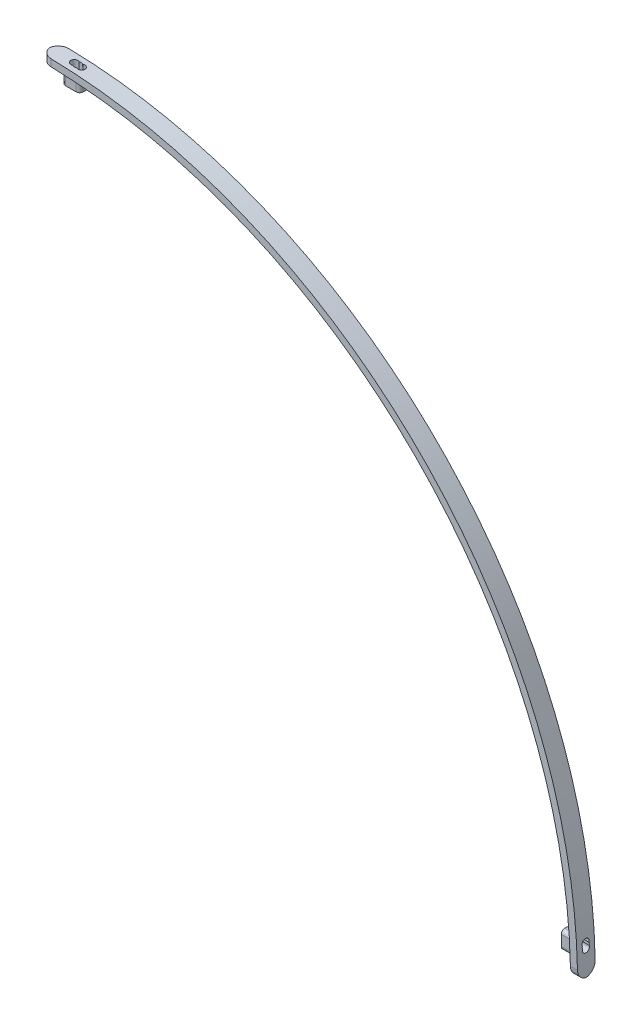
SolidWorks part; units mm, degrees
ref_plane "Front Plane" through (0, 0, 0) normal (0, 0, 1) x (1, 0, 0)
ref_plane "Top Plane" through (0, 0, 0) normal (0, 1, 0) x (1, 0, 0)
ref_plane "Right Plane" through (0, 0, 0) normal (1, 0, 0) x (0, 0, -1)
sketch "Sketch2" plane through (0, 0, 0) normal (0, 1, 0) x (1, 0, 0)
  line L0 (-54.6229, 0) -> (141.9045, 0) construction
  line L1 (0, 100.3842) -> (0, -118.4744) construction
  line L2 (149.7, 2.5) -> (151.7, 2.5)
  line L3 (149.7, 2.5) -> (149.7, -2.5)
  line L4 (149.7, -2.5) -> (151.7, -2.5)
  line L5 (151.7, 2.5) -> (151.7, -2.5)
  line L6 (149.7, 2.5) -> (151.7, -2.5) construction
  line L7 (149.7, -2.5) -> (151.7, 2.5) construction
  point P3 (150.7, 0)
  dimension "D1" = 149.7
  dimension "D2" = 2
  dimension "D3" = 5
revolve "Revolve1" add sketch "Sketch2" angle 90 about L1
fillet "Fillet1" radius 3 4 edges at (0, 150.7, -2.5) (0, 150.7, 2.5) (150.7, 0, -2.5) (150.7, 0, 2.5)
sketch "Sketch3" plane through (0, 0, 0) normal (1, 0, 0) x (0, 0, -1)
  line L0 (0, 10) -> (0, 6) construction
  line L1 (0.75, 10) -> (0.75, 6)
  line L2 (-0.75, 10) -> (-0.75, 6)
  arc A0 (0.75, 10) -> (-0.75, 10) centre (0, 10) ccw
  arc A1 (-0.75, 6) -> (0.75, 6) centre (0, 6) ccw
  point P3 (0, 8)
  point P8 (-0.75, 8)
  dimension "D1" = 6
  dimension "D2" = 4
  dimension "D3" = 1.5
sketch "Sketch5" plane through (0, 0, 0) normal (0, 1, 0) x (1, 0, 0)
  line L0 (2.5, 0) -> (6.5, 0) construction
  line L1 (2.5, 0.75) -> (6.5, 0.75)
  line L2 (2.5, -0.75) -> (6.5, -0.75)
  arc A0 (2.5, 0.75) -> (2.5, -0.75) centre (2.5, 0) ccw
  arc A1 (6.5, -0.75) -> (6.5, 0.75) centre (6.5, 0) ccw
  point P3 (4.5, 0)
  dimension "D1" = 2.5
  dimension "D2" = 1.5
  dimension "D3" = 4
sketch "Sketch6" plane through (0, 0, 0) normal (1, 0, 0) x (0, 0, -1)
  line L0 (0, 14.1133) -> (0, 0) construction
  circle A0 centre (0, 7) radius 1
  circle A1 centre (0, 7.7) radius 1
  circle A2 centre (0, 8.4) radius 1
  dimension "D1" = 2
  dimension "D2" = 7
  dimension "D4" = 0.7
  dimension "D3" = 3
extrude "Cut-Extrude3" cut sketch "Sketch6" against normal through all both and the other way through all contours L0 A2 A1 | L0 A1 A2 | A2 L0 A1 | A1 L0 A2 | A2 A1 A0 | A2 A0 A1 | A0 L0 A1 | L0 A0 A1 | L0 A1 A0 | A1 L0 A0 | A0 region at (0, 8.8521, -0.4898) region at (0, 8.8521, 0.4898) region at (0, 8.2253, -0.4238) region at (0, 8.2253, 0.4238) region at (0, 7.7, 0.8973) region at (0, 7.7, -0.8973) region at (0, 6.5479, 0.4898) region at (0, 7.1747, 0.4238) region at (0, 7.1747, -0.4238) region at (0, 6.5479, -0.4898)
sketch "Sketch8" plane through (0, 0, 0) normal (0, 1, 0) x (1, 0, 0)
  line L0 (-1.8569, 0) -> (9.3157, 0) construction
  circle A0 centre (7.042, 0) radius 1
  circle A1 centre (8.042, 0) radius 1
  circle A2 centre (9.042, 0) radius 1
  dimension "D1" = 3
  dimension "D2" = 7
extrude "Cut-Extrude4" cut sketch "Sketch8" against normal through all both and the other way through all contours L0 A0 A1 | A0 L0 A1 | L0 A1 A0 | A1 L0 A0 | A2 A0 A1 | A2 A1 A0 | A2 L0 A1 | L0 A2 A1 | A1 A2 region at (8.542, 0, -0.3392) region at (7.542, 0, 0.3392) region at (7.542, 0, -0.3392) region at (8.042, 0, 0.7301) region at (8.042, 0, -0.7301) region at (8.542, 0, 0.3392) region at (9.363, 0, 0) region at (6.7209, 0, 0.4791) region at (6.7209, 0, -0.4791)
sketch "Sketch9" plane through (0, 0, 0) normal (1, 0, 0) x (0, 0, -1)
  line L1 (-1, 10.042) -> (1, 10.042)
  line L2 (-2, 9.042) -> (-2, 6.042)
  line L3 (-1, 5.042) -> (1, 5.042)
  line L4 (2, 9.042) -> (2, 6.042)
  arc A0 (-1, 5.042) -> (-2, 6.042) centre (-1, 6.042) cw
  arc A1 (1, 5.042) -> (2, 6.042) centre (1, 6.042) ccw
  arc A2 (-2, 9.042) -> (-1, 10.042) centre (-1, 9.042) cw
  arc A3 (2, 9.042) -> (1, 10.042) centre (1, 9.042) ccw
  point P8 (-2, 5.042)
  point P11 (2, 5.042)
  point P14 (-2, 10.042)
  dimension "D5" = 1
  dimension "D1" = 5
  dimension "D2" = 5
  dimension "D3" = 4
  dimension "D4" = 2
extrude "Boss-Extrude1" add sketch "Sketch9" along normal blind 3.5 from offset 146.6
sketch "Sketch10" plane through (150.1, 0, 0) normal (1, 0, 0) x (0, 0, -1)
  arc A4 (-0.9367, 7.35) -> (0.9367, 7.35) centre (0, 7) ccw
  arc A5 (0.9367, 7.35) -> (0.9367, 8.05) centre (0, 7.7) ccw
  arc A6 (0.9367, 8.05) -> (-0.9367, 8.05) centre (0, 8.4) ccw
  arc A7 (-0.9367, 8.05) -> (-0.9367, 7.35) centre (0, 7.7) ccw
  arc A8 (-0.9367, 7.35) -> (0.9367, 7.35) centre (0, 7) ccw
  arc A9 (0.9367, 7.35) -> (0.9367, 8.05) centre (0, 7.7) ccw
  arc A10 (0.9367, 8.05) -> (-0.9367, 8.05) centre (0, 8.4) ccw
  arc A11 (-0.9367, 8.05) -> (-0.9367, 7.35) centre (0, 7.7) ccw
  dimension "D1" = 0
extrude "Cut-Extrude5" cut sketch "Sketch10" against normal through all both and the other way through all
sketch "Sketch11" plane through (0, 0, 0) normal (0, 1, 0) x (1, 0, 0)
  line L1 (6.542, -2) -> (9.542, -2)
  line L2 (5.542, -1) -> (5.542, 1)
  line L3 (6.542, 2) -> (9.542, 2)
  line L4 (10.542, -1) -> (10.542, 1)
  line L5 (5.542, -2) -> (10.542, 2) construction
  line L6 (5.542, 2) -> (10.542, -2) construction
  arc A0 (9.542, 2) -> (10.542, 1) centre (9.542, 1) cw
  arc A1 (10.542, -1) -> (9.542, -2) centre (9.542, -1) cw
  arc A2 (6.542, 2) -> (5.542, 1) centre (6.542, 1) ccw
  arc A3 (5.542, -1) -> (6.542, -2) centre (6.542, -1) ccw
  point P0 (8.042, 0)
  dimension "D3" = 1
  dimension "D1" = 4
  dimension "D2" = 5
extrude "Boss-Extrude2" add sketch "Sketch11" along normal blind 3.5 from offset 146.6
sketch "Sketch12" plane through (0, 150.1, 0) normal (0, 1, 0) x (1, 0, 0)
  arc A4 (7.542, -0.866) -> (8.542, -0.866) centre (8.042, 0) ccw
  arc A5 (8.542, -0.866) -> (8.542, 0.866) centre (9.042, 0) ccw
  arc A6 (8.542, 0.866) -> (7.542, 0.866) centre (8.042, 0) ccw
  arc A7 (7.542, 0.866) -> (7.542, -0.866) centre (7.042, 0) ccw
  arc A8 (7.542, -0.866) -> (8.542, -0.866) centre (8.042, 0) ccw
  arc A9 (8.542, -0.866) -> (8.542, 0.866) centre (9.042, 0) ccw
  arc A10 (8.542, 0.866) -> (7.542, 0.866) centre (8.042, 0) ccw
  arc A11 (7.542, 0.866) -> (7.542, -0.866) centre (7.042, 0) ccw
  dimension "D1" = 0
extrude "Cut-Extrude6" cut sketch "Sketch12" against normal through all both and the other way through all
